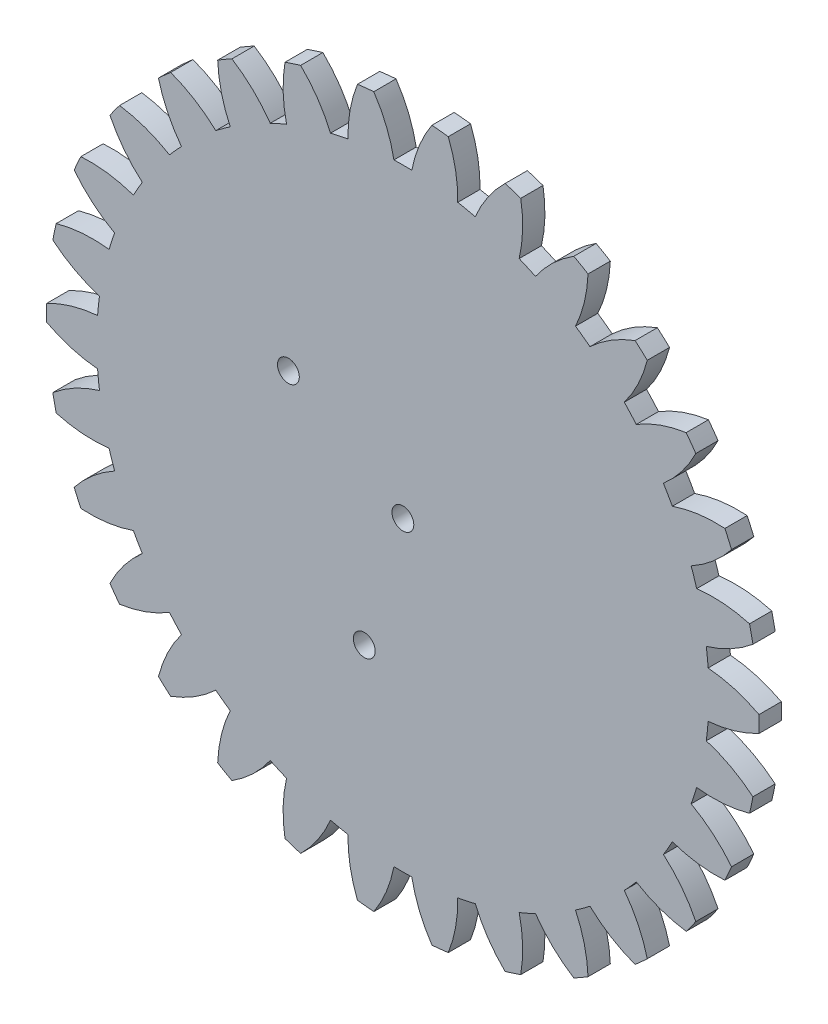
SolidWorks part; units mm, degrees
ref_plane "Front Plane" through (0, 0, 0) normal (0, 0, 1) x (1, 0, 0)
ref_plane "Top Plane" through (0, 0, 0) normal (0, 1, 0) x (1, 0, 0)
ref_plane "Right Plane" through (0, 0, 0) normal (1, 0, 0) x (0, 0, -1)
sketch "Sketch1" plane through (0, 0, 0) normal (0, 0, 1) x (1, 0, 0)
  line L0 (-8.9062, -3.9676) -> (0, 0) construction
  circle A0 centre (0, 0) radius 48
  dimension "D1" = 96
extrude "Boss-Extrude1" add sketch "Sketch1" along normal blind 3
sketch "Sketch2" plane through (0, 0, 3) normal (0, 0, 1) x (1, 0, 0)
  line L0 (0, 0) -> (0, 48) construction
  line L1 (0, 0) -> (-5.0174, 47.7371) construction
  line L2 (-2.3411, 44.9391) -> (-4.6973, 44.6914) construction
  circle A0 centre (0, 0) radius 41.25 construction
  circle A1 centre (0, 0) radius 42.2862 construction
  circle A2 centre (0, 0) radius 45 construction
  circle A5 centre (0, 0) radius 48 construction
  arc A6 (-1.2039, 41.2324) -> (1.2039, 41.2324) centre (0, 0) cw
  arc A7 (-3.9161, 47.84) -> (3.9161, 47.84) centre (0, 0) cw
  arc A8 (-3.9161, 47.84) -> (-1.2039, 41.2324) centre (-18.8807, 37.837) cw
  arc A9 (1.2039, 41.2324) -> (3.9161, 47.84) centre (18.8807, 37.837) cw
  dimension "D1" = 82.5
  dimension "D2" = 84.5723
  dimension "D3" = 90
  dimension "D5" = 18
  dimension "D6" = 18
  dimension "D4" = 6
  dimension "D7" = 2.3562
extrude "Cut-Extrude1" cut sketch "Sketch2" against normal through all
pattern_circular "CirPattern1" count 30 over 360 about axis through (0, 0, 3) along (0, 0, 1) of face at (-2.3945, 44.6041, 1.5) of face at (0, 41.2412, 1.5) of face at (2.3945, 44.6041, 1.5)
ref_axis "Axis1" through (0, 0, 0) along (0, 0, 1)
sketch "Sketch7" plane through (0, 0, 0) normal (0, 0, -1) x (-1, 0, 0)
  circle A0 centre (0, 0) radius 1.47
  dimension "D1" = 2.94
extrude "Cut-Extrude2" cut sketch "Sketch7" against normal through all contours A0
sketch "Sketch8" plane through (0, 0, 0) normal (0, 0, -1) x (-1, 0, 0)
  line L0 (0, 0) -> (9.396, -31.3732) construction
  line L1 (0, 0) -> (27.8723, 17.1958) construction
  circle A2 centre (5.2001, -17.363) radius 1.47
  circle A4 centre (15.4255, 9.5167) radius 1.47
  circle A5 centre (0, 0) radius 1.47 construction
  dimension "D1" = 2.94
  dimension "D2" = 2.94
  dimension "D4" = 18.125
  dimension "D3" = 18.125
extrude "Cut-Extrude3" cut sketch "Sketch8" against normal through all
equation "\"module\"= 3.0"
equation "\"teeth\"= 30"
equation "\"pressureAngle\"= 20deg"
equation "\"gearThickness\"= 3"
equation "\"addendumFactor\"= 1"
equation "\"dedendumFactor\"= 1.25"
equation "\"pitch\"= 1 / \"module\""
equation "\"pitchDiameter\"= \"teeth\" / \"pitch\""
equation "\"addendum\"= \"addendumFactor\" / \"pitch\""
equation "\"dedendum\"= \"dedendumFactor\" / \"pitch\""
equation "\"D1@Sketch1\"=\"pitchDiameter\" + 2 * \"addendum\""
equation "\"D1@Boss-Extrude1\"=\"gearThickness\""
equation "\"D1@Sketch2\"=\"pitchDiameter\" - 2 * \"dedendum\""
equation "\"D2@Sketch2\"=\"pitchDiameter\" * cos(\"pressureAngle\")"
equation "\"D3@Sketch2\"=\"pitchDiameter\""
equation "\"D4@Sketch2\"=180/\"teeth\""
equation "\"D5@Sketch2\"=\"pitchDiameter\"/5"
equation "\"D6@Sketch2\"=\"pitchDiameter\"/5"
equation "\"D7@Sketch2\"= PI / 2 / \"pitch\"/2"
equation "\"D1@CirPattern1\"=\"teeth\""
